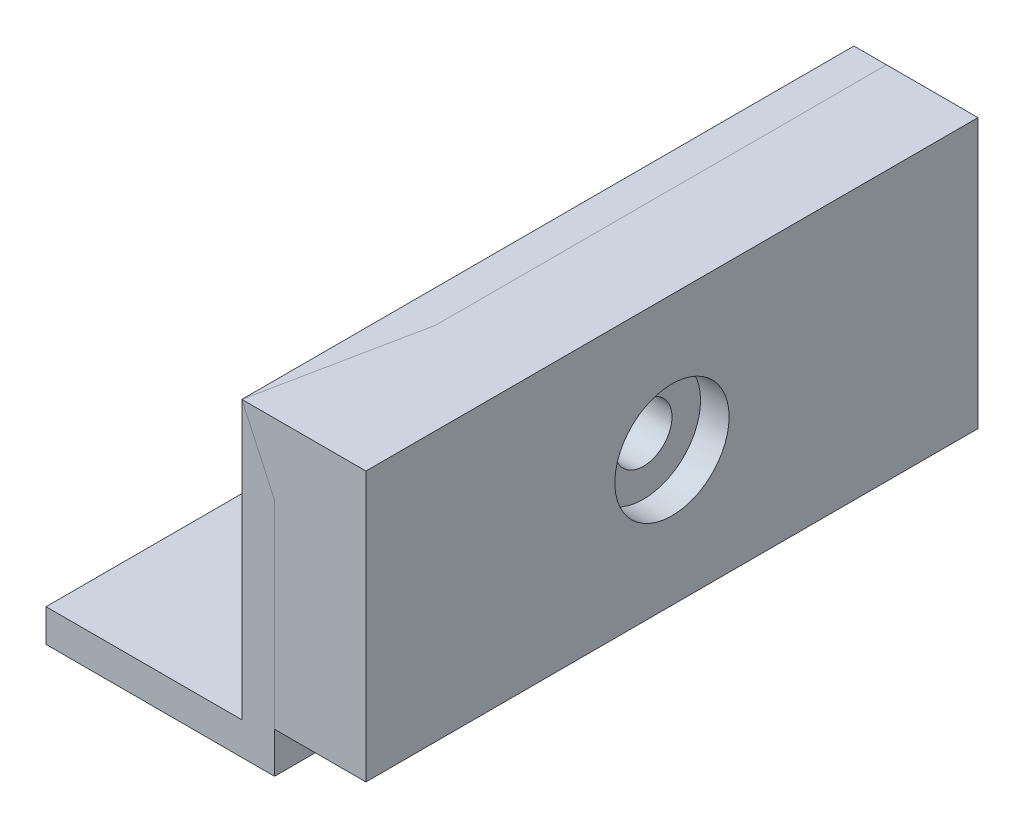
SolidWorks part; units mm, degrees
material "AISI 1020 Steel, Cold Rolled"
ref_plane "Front Plane" through (0, 0, 0) normal (0, 0, 1) x (1, 0, 0)
ref_plane "Top Plane" through (0, 0, 0) normal (0, 1, 0) x (1, 0, 0)
ref_plane "Right Plane" through (0, 0, 0) normal (1, 0, 0) x (0, 0, -1)
sketch "Sketch1" plane through (0, 0, 0) normal (1, 0, 0) x (0, 0, -1)
  line L1 (-37.5, 16.5) -> (37.5, 16.5)
  line L2 (-37.5, 16.5) -> (-37.5, -16.5)
  line L3 (-37.5, -16.5) -> (37.5, -16.5)
  line L4 (37.5, 16.5) -> (37.5, -16.5)
  line L5 (0, -16.5) -> (0, 16.5) construction
  line L6 (-37.5, 0) -> (37.5, 0) construction
  circle A0 centre (0, 0) radius 3.5
  point P0 (0, 0)
  dimension "D3" = 7
  dimension "D1" = 75
  dimension "D2" = 33
extrude "Boss-Extrude1" add sketch "Sketch1" along normal blind 11.2
sketch "Sketch2" plane through (11.2, 0, 0) normal (1, 0, 0) x (0, 0, -1)
  circle A0 centre (0, 0) radius 7
  dimension "D1" = 14
extrude "Cut-Extrude1" cut sketch "Sketch2" against normal blind 3.5
sketch "Sketch3" plane through (0, 0, 0) normal (-1, 0, 0) x (0, 0, 1)
  line L0 (-37.5, 16.5) -> (37.5, 16.5) construction
  line L1 (0, -16.5) -> (-37.5, -16.5) construction
  line L2 (37.5, -16.5) -> (37.5, 16.5)
  line L3 (37.5, 16.5) -> (-37.5, 16.5)
  line L4 (-37.5, -16.5) -> (-37.5, 16.5)
  line L5 (0, 16.5) -> (0, -16.5) construction
  line L6 (37.5, 0) -> (-37.5, 0) construction
  line L8 (37.5, 16.5) -> (-37.5, 16.5)
  line L12 (0, -16.5) -> (-37.5, -16.5) construction
  line L13 (37.5, -16.5) -> (37.5, -21.5)
  line L14 (37.5, -21.5) -> (-37.5, -21.5)
  line L15 (-37.5, -16.5) -> (-37.5, -21.5)
  line L16 (37.5, -21.5) -> (-37.5, -21.5)
  line L17 (37.5, -21.5) -> (37.5, 16.5)
  line L18 (37.5, 16.5) -> (-37.5, 16.5)
  line L19 (-37.5, -21.5) -> (-37.5, 16.5)
  circle A0 centre (0, 0) radius 3.5
  point P0 (0, 0)
  line M6 (-37.5, -16.5) -> (37.5, -16.5)
  line M8 (37.5, 16.5) -> (-37.5, 16.5)
  circle M9 centre (0, 0) radius 3.5
  dimension "D1" = 75
  dimension "D2" = 5
extrude "Boss-Extrude2" add sketch "Sketch3" along normal blind 4 contours L4 L2 M6 M8 M9 | M8 region at (0, -15.6806, 0)
extrude "Boss-Extrude4" add sketch "Sketch3<3>" along normal blind 4 separate body contours L4 L2 M6 M8 M9 | L15 L14 L13 M6 region at (0, -15.6806, 0) region at (0, -19, 0)
sketch "Sketch3<3>" plane through (0, 0, 0) normal (-1, 0, 0) x (0, 0, 1) same geometry as "Sketch3"
sketch "Sketch6" plane through (-4, 0, 0) normal (-1, 0, 0) x (0, 0, 1)
  line L0 (-37.5, 16.5) -> (-37.5, -21.5) construction
  line L1 (37.5, -21.5) -> (-37.5, -21.5)
  line L2 (37.5, -21.5) -> (37.5, -17.498)
  line L3 (37.5, -17.498) -> (-37.5, -17.498)
  line L4 (-37.5, -21.5) -> (-37.5, -17.498)
  dimension "D1" = 4.002
extrude "Boss-Extrude6" add sketch "Sketch6" along normal blind 24
